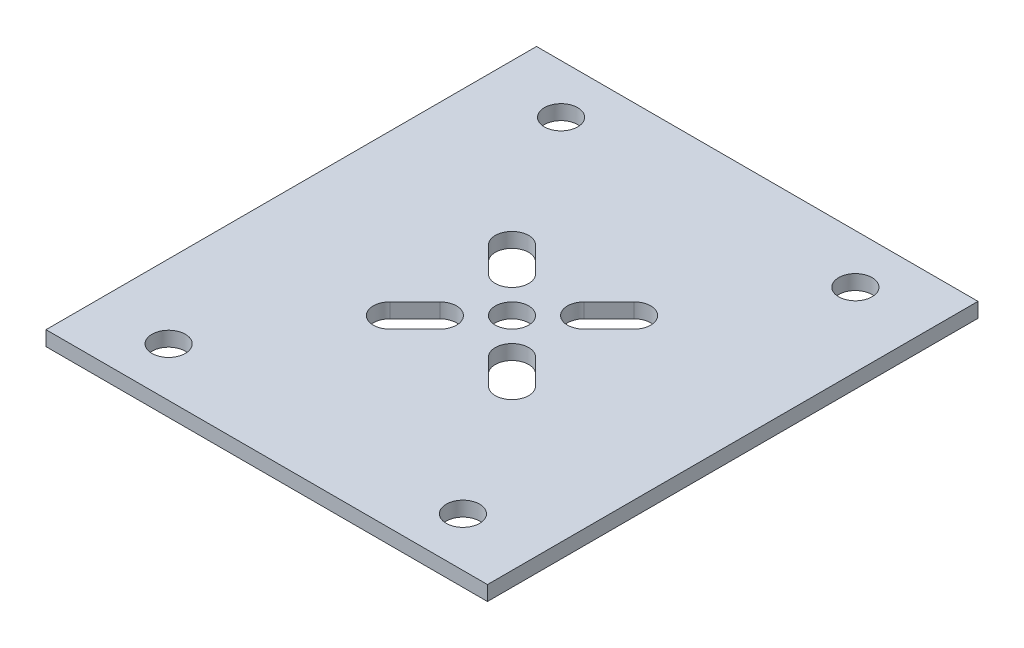
SolidWorks part; units mm, degrees
material "Thornel Mat VMA"
ref_plane "Front Plane" through (0, 0, 0) normal (0, 0, 1) x (1, 0, 0)
ref_plane "Top Plane" through (0, 0, 0) normal (0, 1, 0) x (1, 0, 0)
ref_plane "Right Plane" through (0, 0, 0) normal (1, 0, 0) x (0, 0, -1)
sketch "Sketch2" plane through (0, 0, 0) normal (0, 1, 0) x (1, 0, 0)
  line L1 (-22.5, -25) -> (22.5, -25)
  line L2 (-22.5, -25) -> (-22.5, 25)
  line L3 (-22.5, 25) -> (22.5, 25)
  line L4 (22.5, -25) -> (22.5, 25)
  point P0 (0, 0)
  dimension "D1" = 50
  dimension "D2" = 45
  dimension "D3" = 22.5
  dimension "D4" = 25
extrude "Boss-Extrude1" add sketch "Sketch2" along normal blind 1.5
hole_wizard "M3 Clearance Hole" positions "Sketch7" profile "Sketch8" hole size "M3" standard "ANSI Metric" end condition up to next
sketch "Sketch7" plane through (0, 1.5, 0) normal (0, 1, 0) x (1, 0, 0)
  point P0 (-15, 20)
  point P2 (15, 20)
  point P4 (15, -20)
  point P6 (-15, -20)
  point P16 (0, 0)
  dimension "D1" = 20
  dimension "D2" = 30
  dimension "D3" = 40
  dimension "D4" = 15
sketch "Sketch8" plane through (-15, 1.5, -20) normal (1, 0, 0) x (0, 0, 1)
  line L0 (0, 0) -> (0, 1.5)
  line L1 (0, 1.5) -> (1.7, 1.5)
  line L2 (1.7, 1.5) -> (1.7, 0)
  line L5 (1.7, 0) -> (0, 0)
  line L11 (0, -6.35) -> (0, 107.95) construction
  dimension "Thru Hole Dia." = 3.4
  dimension "Thru Hole Depth" = 1.5
hole_wizard "M3 Clearance Slot1" positions "Sketch11" profile "Sketch12" size "M3" standard "ANSI Metric" slot yes end condition up to next
sketch "Sketch11" plane through (0, 1.5, 0) normal (0, 1, 0) x (1, 0, 0)
  line L1 (-7.4246, 7.4246) -> (-2.4749, 2.4749) construction
  line L2 (-22.5, 25) -> (-22.5, -25) construction
  line L3 (-2.4749, 2.4749) -> (4.9497, -4.9497) construction
  point P0 (-4.9497, 4.9497)
  point P13 (4.9497, -4.9497)
  point P28 (5.5602, -8.1059)
  point P29 (11.9673, -14.6904)
  point P30 (16.1722, -10.0193)
  point P32 (6.2103, -6.2103)
  point P33 (-1.9058, 1.9058)
  point P34 (4.9497, -4.9497)
  dimension "D1" = 7
  dimension "D2" = 45
  dimension "D3" = 7
  dimension "D4" = 7
sketch "Sketch12" plane through (-4.9497, 1.5, -4.9497) normal (1, 0, 0) x (0, 0, 1)
  line L0 (0, 0) -> (0, 1.5)
  line L1 (0, 1.5) -> (1.7, 1.5)
  line L2 (1.7, 1.5) -> (1.7, 0)
  line L5 (1.7, 0) -> (0, 0)
  line L11 (0, -6.35) -> (0, 107.95) construction
  dimension "Thru Hole Dia." = 3.4
  dimension "Thru Hole Depth" = 1.5
hole_wizard "M3 Clearance Slot2" positions "Sketch13" profile "Sketch14" size "M3" standard "ANSI Metric" slot yes end condition up to next
sketch "Sketch13" plane through (0, 1.5, 0) normal (0, 1, 0) x (1, 0, 0)
  line L0 (2.4749, 2.4749) -> (7.4246, 7.4246) construction
  line L1 (22.5, -25) -> (22.5, 25) construction
  line L2 (2.4749, 2.4749) -> (-4.9497, -4.9497) construction
  point P0 (4.9497, 4.9497)
  point P4 (-4.9497, -4.9497)
  dimension "D1" = 7
  dimension "D2" = 45
  dimension "D3" = 7
  dimension "D4" = 7
sketch "Sketch14" plane through (4.9497, 1.5, -4.9497) normal (1, 0, 0) x (0, 0, 1)
  line L0 (0, 0) -> (0, 1.5)
  line L1 (0, 1.5) -> (1.7, 1.5)
  line L2 (1.7, 1.5) -> (1.7, 0)
  line L5 (1.7, 0) -> (0, 0)
  line L11 (0, -6.35) -> (0, 107.95) construction
  dimension "Thru Hole Dia." = 3.4
  dimension "Thru Hole Depth" = 1.5
